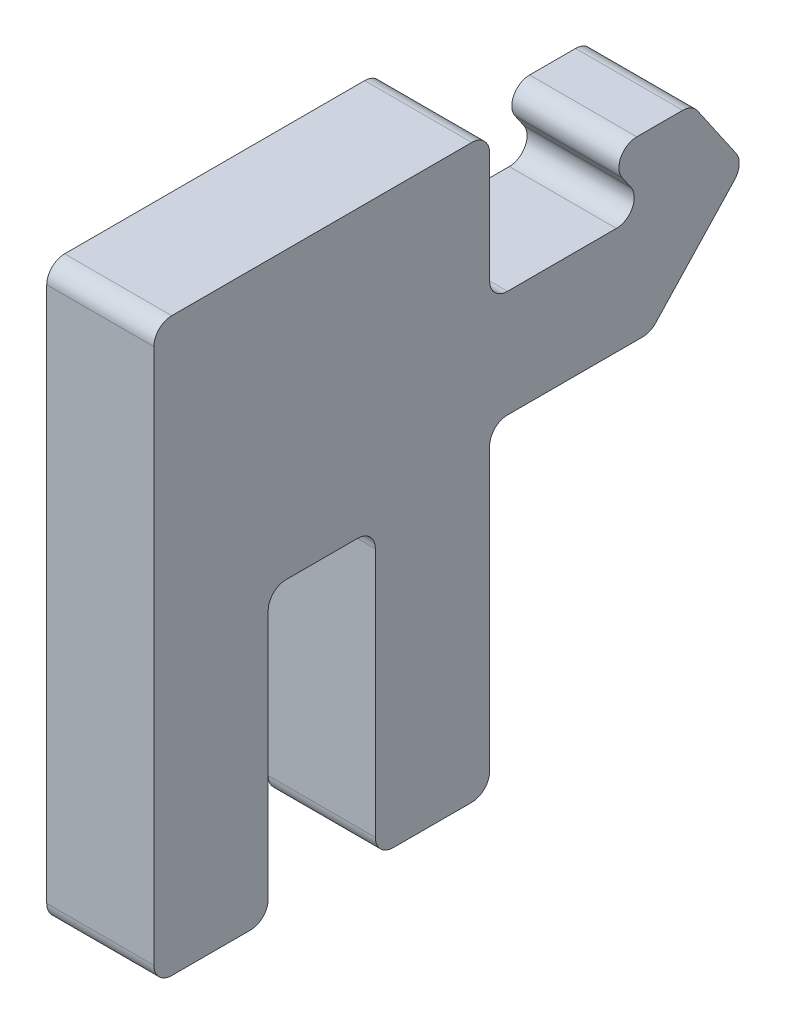
SolidWorks part; units mm, degrees
ref_plane "Alzado" through (0, 0, 0) normal (0, 0, 1) x (1, 0, 0)
ref_plane "Planta" through (0, 0, 0) normal (0, 1, 0) x (1, 0, 0)
ref_plane "Vista lateral" through (0, 0, 0) normal (1, 0, 0) x (0, 0, -1)
sketch "Croquis1" plane through (0, 0, 0) normal (1, 0, 0) x (0, 0, -1)
  line L1 (-4.7, 8) -> (4.7, 8)
  line L2 (-4.7, 8) -> (-4.7, -8)
  line L3 (-4.7, -8) -> (4.7, -8)
  line L16 (4.7, 8) -> (4.7, -8)
  dimension "D1" = 4.7
  dimension "D2" = 8
  dimension "D3" = 16
  dimension "D4" = 9.4
extrude "Saliente-Extruir1" add sketch "Croquis1" along normal blind 3
sketch "Croquis2" plane through (3, 0, 0) normal (1, 0, 0) x (0, 0, -1)
  line L0 (0, 0) -> (0, -9.3656) construction
  line L1 (-4.7, -8) -> (4.7, -8) construction
  line L2 (-1.5, -8) -> (1.5, -8)
  line L3 (-1.5, -8) -> (-1.5, 0)
  line L4 (-1.5, 0) -> (1.5, 0)
  line L5 (1.5, -8) -> (1.5, 0)
  dimension "D1" = 1.5
  dimension "D2" = 1.5
  dimension "D3" = 8
extrude "Cortar-Extruir1" cut sketch "Croquis2" against normal up to surface (3 mm away) up to face at (0, 0, 0)
sketch "Croquis4" plane through (3, 0, 0) normal (1, 0, 0) x (0, 0, -1)
  line L9 (1.5, 0) -> (-1.5, 0) construction
  line L10 (0, 0) -> (0, 10.8389) construction
  line L18 (4.7, 3.8918) -> (4.7, 0.8918)
  line L19 (4.7, -8) -> (4.7, 8) construction
  line L20 (4.7, 0.8918) -> (9.2, 0.8918)
  line L22 (9.2, 3.8918) -> (4.7, 3.8918)
  line L25 (7.8691, 5.8274) -> (9.2, 3.8918)
  line L26 (7.8691, 5.8274) -> (10.3691, 5.8274)
  line L27 (10.3691, 5.8274) -> (11.8287, 3.7046)
  line L28 (11.8287, 3.7046) -> (9.2, 0.8918)
  dimension "D1" = 4.5
  dimension "D2" = 3
  dimension "D3" = 4.5
  dimension "D4" = 3.8918
  dimension "D5" = 5.8274
  dimension "D6" = 6.1126
  dimension "D7" = 2.5
  dimension "D8" = 11.8459
extrude "Saliente-Extruir2" add sketch "Croquis4" against normal up to surface (3 mm away) up to face at (0, -2, 0)
fillet "Redondeo1" radius 0.5 15 edges at (1.5, 8, 4.7) (1.5, 3.8918, -4.7) (1.5, 8, -4.7) (1.5, 5.8274, -7.8691) (1.5, 5.8274, -10.3691) (1.5, 3.7046, -11.8287) (1.5, 0.8918, -9.2) (1.5, 0.8918, -4.7) (1.5, 0, -1.5) (1.5, 0, 1.5) (1.5, -8, 1.5) (1.5, -8, 4.7) (1.5, -8, -4.7) (1.5, -8, -1.5) (1.5, 3.8918, -9.2)
